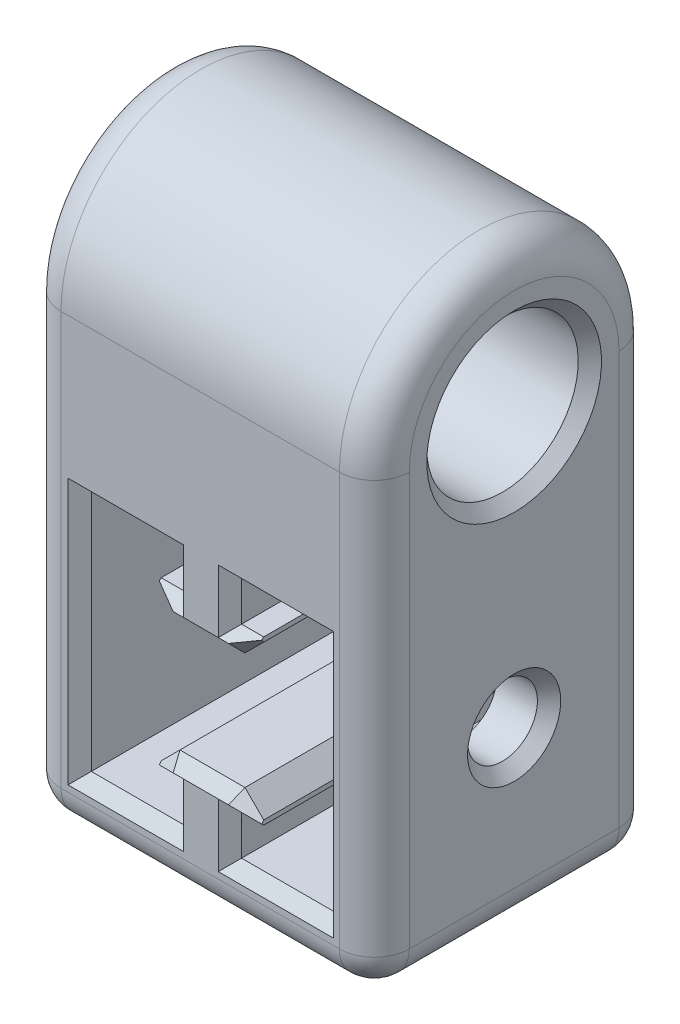
SolidWorks part; units mm, degrees
ref_plane "Front Plane" through (0, 0, 0) normal (0, 0, 1) x (1, 0, 0)
ref_plane "Top Plane" through (0, 0, 0) normal (0, 1, 0) x (1, 0, 0)
ref_plane "Right Plane" through (0, 0, 0) normal (1, 0, 0) x (0, 0, -1)
sketch "Sketch1" plane through (0, 0, 0) normal (0, 0, 1) x (1, 0, 0)
  line L0 (0, -15) -> (0, 15) construction
  line L1 (0, 15) -> (14.8993, 15)
  line L2 (14.8993, 15) -> (14.8993, -14.9496)
  line L3 (14.8993, -14.9496) -> (-15, -14.9496)
  line L4 (-15, -14.9496) -> (-15, 15)
  line L5 (-15, 15) -> (0, 15)
  line L6 (0, -10.4) -> (0, 10.4) construction
  line L7 (0, 10.4) -> (-10.4, 10.4) construction
  line L8 (-10.4, 10.4) -> (-2.5, 10.4)
  line L9 (-2.5, 10.4) -> (-2.5, 7)
  line L10 (-2.5, 7) -> (0, 7) construction
  line L11 (-2.5, 7) -> (-4.4, 7)
  line L12 (-4.4, 7) -> (-4.4, 6.61)
  line L13 (-4.4, 6.61) -> (-2.79, 5)
  line L14 (-2.79, 5) -> (0, 5) construction
  line L15 (-2.79, 5) -> (2.79, 5)
  line L16 (10.4, 2.9336) -> (10.4, -2.9336)
  line L22 (-10.4, 10.4) -> (-10.4, 2.9336)
  line L23 (0, 0) -> (-11.0308, 0) construction
  line L24 (4.4, 6.61) -> (2.79, 5)
  line L25 (4.4, 7) -> (4.4, 6.61)
  line L26 (2.5, 7) -> (4.4, 7)
  line L27 (2.5, 10.4) -> (2.5, 7)
  line L28 (10.4, 10.4) -> (2.5, 10.4)
  line L29 (10.4, 10.4) -> (10.4, 2.9336)
  line L35 (-10.4, -10.4) -> (0, 0) construction
  line L36 (-2.79, -5) -> (0, -5) construction
  line L37 (-2.5, -7) -> (0, -7) construction
  line L38 (0, -10.4) -> (-10.4, -10.4) construction
  line L43 (10.4, -10.4) -> (10.4, -2.9336)
  line L44 (10.4, -10.4) -> (2.5, -10.4)
  line L45 (2.5, -10.4) -> (2.5, -7)
  line L46 (2.5, -7) -> (4.4, -7)
  line L47 (4.4, -7) -> (4.4, -6.61)
  line L48 (4.4, -6.61) -> (2.79, -5)
  line L49 (-10.4, -10.4) -> (-10.4, -2.9336)
  line L54 (-2.79, -5) -> (2.79, -5)
  line L55 (-4.4, -6.61) -> (-2.79, -5)
  line L56 (-4.4, -7) -> (-4.4, -6.61)
  line L57 (-2.5, -7) -> (-4.4, -7)
  line L58 (-2.5, -10.4) -> (-2.5, -7)
  line L59 (-10.4, -10.4) -> (-2.5, -10.4)
  line L60 (-10.4, 2.9336) -> (-10.4, -2.61)
  line L61 (-10.4, -2.61) -> (-10.4, -2.9336)
  point P43 (5, 0)
  point P58 (-5, 0)
  dimension "D1" = 2.5
  dimension "D2" = 2.79
  dimension "D3" = 1.9
  dimension "D4" = 135
  dimension "D5" = 2
  dimension "D6" = 15
  dimension "D7" = 15
  dimension "D8" = 10.4
  dimension "D9" = 90
  dimension "D10" = 3.4
  dimension "D11" = 10.4
extrude "Boss-Extrude1" add sketch "Sketch1" along normal blind 24
sketch "Sketch5" plane through (-15, 0, 0) normal (-1, 0, 0) x (0, 0, 1)
  line L2 (0, 15) -> (24, 15)
  line L10 (0, 23.5) -> (0, 15)
  line L11 (12, 17) -> (12, 23.5) construction
  line L13 (24, 23.5) -> (24, 15)
  circle A2 centre (12, 23.5) radius 6.5
  arc A3 (0, 23.5) -> (24, 23.5) centre (12, 23.5) cw
  dimension "D3" = 13
  dimension "D5" = 6.5
  dimension "D4" = 2
  dimension "D6" = 12
extrude "Boss-Extrude3" add sketch "Sketch5" against normal through all
sketch "Sketch3" plane through (-15, 0, 0) normal (-1, 0, 0) x (0, 0, 1)
  line L0 (12, 0) -> (24, 4.2752) construction
  line L2 (0, 0) -> (12, 0) construction
  line L3 (24, 23.5) -> (24, -14.9496) construction
  circle A0 centre (12, 0) radius 3
extrude "Cut-Extrude1" cut sketch "Sketch3" against normal through all
sketch "Sketch6" plane through (-15, 0, 0) normal (-1, 0, 0) x (0, 0, 1)
  line L0 (12.4083, 17.0128) -> (12, 23.5) construction
  circle A0 centre (12, 23.5) radius 6.5 construction
  circle A1 centre (12, 23.5) radius 5
  circle A2 centre (12, 23.5) radius 12
extrude "Boss-Extrude4" add sketch "Sketch6" against normal blind 4
fillet "Fillet1" radius 3 10 edges at (-0.0504, -14.9496, 24) (14.8993, 4.2752, 24) (-15, 4.2752, 24) (14.8993, 4.2752, 0) (-15, 4.2752, 0) (-0.0504, -14.9496, 0) (14.8993, -14.9496, 12) (-15, -14.9496, 12) (-15, 35.5, 12) (14.8993, 35.5, 12)
chamfer "Chamfer1" distance 1 angle 45 44 edges at (-15, 0, 15) (14.8993, 0, 15) (14.8993, 23.5, 18.5) (-3.595, 5.805, 0) (0, 5, 0) (3.595, 5.805, 0) (3.45, 7, 0) (2.5, 8.7, 0) (6.45, 10.4, 0) (10.4, 0, 0) (6.45, -10.4, 0) (2.5, -8.7, 0) (3.45, -7, 0) (3.595, -5.805, 0) (0, -5, 0) (-3.595, -5.805, 0) (-3.45, -7, 0) (-2.5, -8.7, 0) (-6.45, -10.4, 0) (-10.4, 0, 0) (-6.45, 10.4, 0) (-2.5, 8.7, 0) (-3.45, 7, 0) (-2.5, 8.7, 24) (-6.45, 10.4, 24) (-10.4, 0, 24) (-6.45, -10.4, 24) (-2.5, -8.7, 24) (-3.45, -7, 24) (-3.595, -5.805, 24) (0, -5, 24) (3.595, -5.805, 24) (3.45, -7, 24) (2.5, -8.7, 24) (6.45, -10.4, 24) (10.4, 0, 24) (6.45, 10.4, 24) (2.5, 8.7, 24) (3.45, 7, 24) (3.595, 5.805, 24) (0, 5, 24) (-3.595, 5.805, 24) (-3.45, 7, 24) (-15, 23.5, 17)
